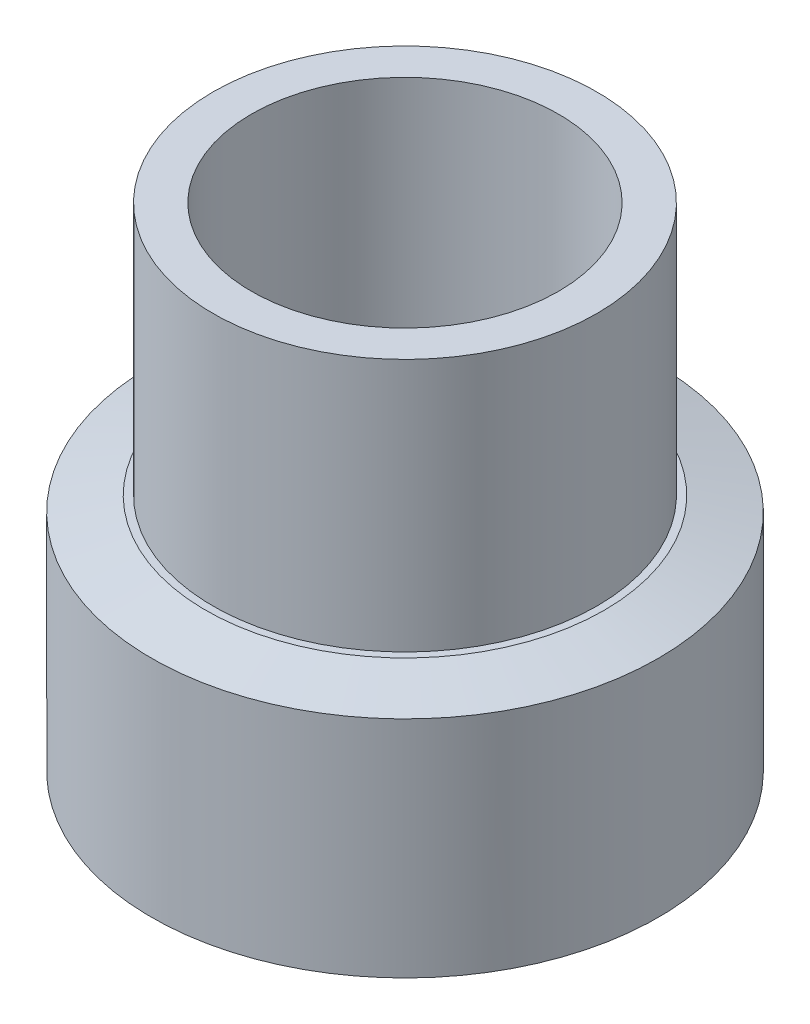
SolidWorks part; units mm, degrees
material "Сталь ШХ15 ГОСТ 801-78"
ref_plane "Plane1" through (0, 0, 0) normal (0, 0, 1) x (1, 0, 0)
ref_plane "Plane2" through (0, 0, 0) normal (0, 1, 0) x (1, 0, 0)
ref_plane "Plane3" through (0, 0, 0) normal (1, 0, 0) x (0, 0, -1)
sketch "Эскиз2" plane through (0, 0, 0) normal (0, 0, 1) x (1, 0, 0)
  line L0 (0, 0) -> (3.3, 0)
  line L1 (3.3, 0) -> (3.3, 3.3)
  line L2 (3.3, 3.3) -> (2.5, 3.3)
  line L3 (2.5, 3.3) -> (2.5, 6.6)
  line L4 (2.5, 6.6) -> (0, 6.6)
  line L5 (0, 6.6) -> (0, 0)
  dimension "D1" = 3.3
  dimension "D2" = 3.3
  dimension "D3" = 3.3
  dimension "D4" = 2.5
ref_axis "Ось1" through (0, 6.6, 0) along (0, -1, 0)
revolve "Повернуть2" add sketch "Эскиз2" angle 360 about axis through (0, 6.6, 0) along (0, -1, 0)
chamfer "Фаска2" distance 0.705 angle 15 1 edges at (-3.3, 3.3, 0) first distance on face at (-2.5, 3.3, 0)
chamfer "Фаска3" distance 0.705 angle 15 1 edges at (-3.3, 0, 0) first distance on face at (-3.3, 0, 0)
sketch "Эскиз3" plane through (0, 0, 0) normal (0, 0, 1) x (1, 0, 0)
  circle A0 centre (0, 8.027) radius 1
sketch "Эскиз4" plane through (0, 6.6, 0) normal (0, 1, 0) x (1, 0, 0)
  circle A0 centre (0, 0) radius 2
  dimension "D1" = 4
extrude "Вырез-Вытянуть2" cut sketch "Эскиз4" against normal through all both contours A0
